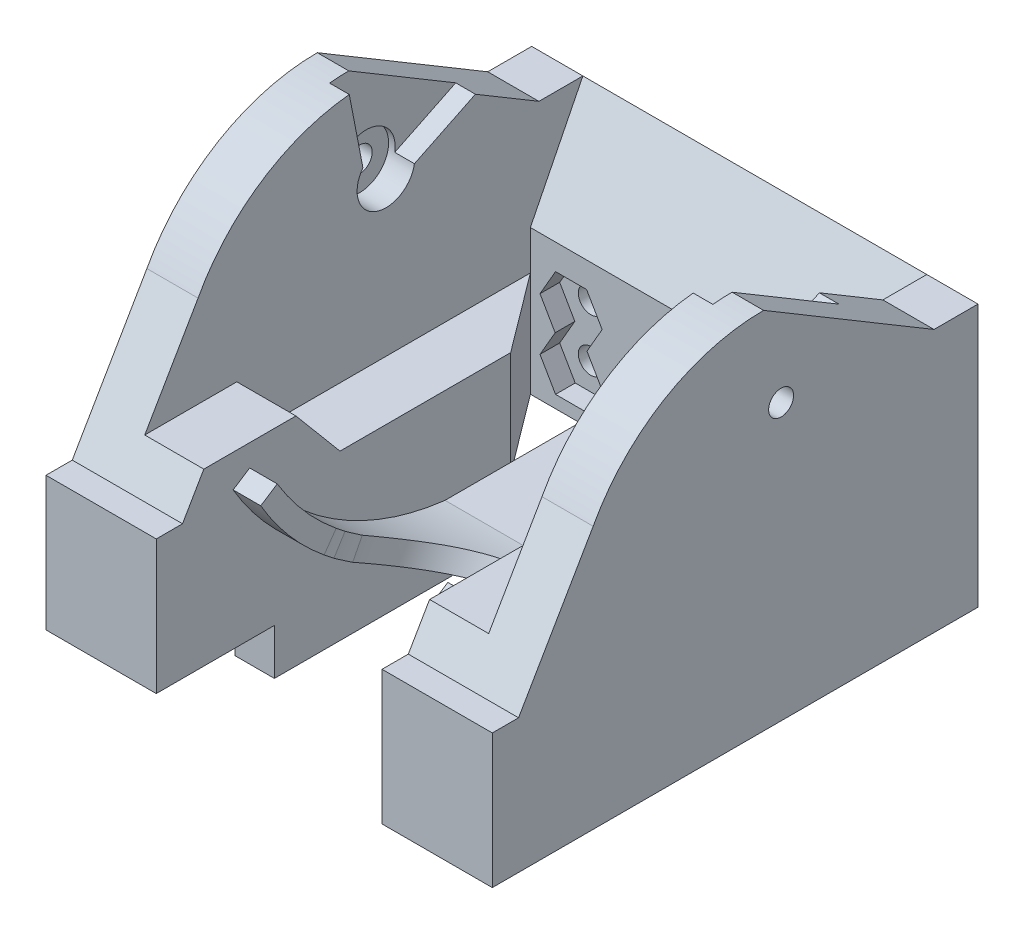
SolidWorks part; units mm, degrees
ref_plane "Alzado" through (0, 0, 0) normal (0, 0, 1) x (1, 0, 0)
ref_plane "Planta" through (0, 0, 0) normal (0, 1, 0) x (1, 0, 0)
ref_plane "Vista lateral" through (0, 0, 0) normal (1, 0, 0) x (0, 0, -1)
sketch "Croquis1" plane through (0, 0, 0) normal (0, 0, 1) x (1, 0, 0)
  line L1 (-48.8873, 14.6225) -> (-14.8873, 14.6225)
  line L2 (-48.8873, 14.6225) -> (-48.8873, -4.3775)
  line L3 (-48.8873, -4.3775) -> (-14.8873, -4.3775)
  line L4 (-14.8873, 14.6225) -> (-14.8873, -4.3775)
  dimension "D1" = 19
  dimension "D2" = 34
extrude "Saliente-Extruir1" add sketch "Croquis1" along normal blind 35
sketch "Croquis2" plane through (0, -4.3775, 0) normal (0, -1, 0) x (1, 0, 0)
  line L0 (-48.8873, 35) -> (-14.8873, 35) construction
  line L1 (-44.9873, 35) -> (-18.7873, 35)
  line L2 (-44.9873, 35) -> (-44.9873, 4)
  line L3 (-44.9873, 4) -> (-18.7873, 4)
  line L4 (-18.7873, 35) -> (-18.7873, 4)
  line L5 (-48.8873, 35) -> (-48.8873, 0) construction
  line L6 (-14.8873, 35) -> (-14.8873, 0) construction
  line L7 (-48.8873, 0) -> (-14.8873, 0) construction
  dimension "D1" = 3.9
  dimension "D2" = 3.9
  dimension "D3" = 26.2
  dimension "D4" = 4
extrude "Cortar-Extruir1" cut sketch "Croquis2" against normal blind 25
sketch "Croquis4" plane through (-18.7873, 0, 0) normal (-1, 0, 0) x (0, 0, 1)
  line L0 (4, 14.6225) -> (4, 6.6225)
  line L1 (4, 14.6225) -> (4, -4.3775) construction
  line L2 (4, 6.6225) -> (0, 14.6225)
  line L3 (0, 14.6225) -> (4, 14.6225)
extrude "Cortar-Extruir3" cut sketch "Croquis4" along normal up to vertex (26.2 mm away) up to point (-44.9873, 14.6225, 4)
sketch "Croquis9" plane through (-14.8873, 0, 0) normal (1, 0, 0) x (0, 0, -1)
  line L0 (-35, 14.6225) -> (0, 14.6225) construction
  line L1 (-29.3158, 14.6225) -> (-3.3495, 14.6225)
  line L7 (-35, -4.3775) -> (0, -4.3775) construction
  arc A0 (-29.3158, 14.6225) -> (-3.3495, 14.6225) centre (-16.3327, 7.6225) cw
  dimension "D2" = 12
extrude "Saliente-Extruir2" add sketch "Croquis9" against normal up to vertex (34 mm away) up to point (-48.8873, 14.6225, 35)
sketch "Croquis10" plane through (0, 14.6225, 0) normal (0, -1, 0) x (1, 0, 0)
  line L1 (-44.9873, 29.3158) -> (-18.7873, 29.3158)
  line L2 (-44.9873, 29.3158) -> (-44.9873, 3.3495)
  line L3 (-44.9873, 3.3495) -> (-18.7873, 3.3495)
  line L4 (-18.7873, 29.3158) -> (-18.7873, 3.3495)
extrude "Cortar-Extruir4" cut sketch "Croquis10" against normal blind 10
sketch "Croquis18" plane through (0, 0, 0) normal (0, 0, -1) x (-1, 0, 0)
  line L0 (48.8873, -4.3775) -> (14.8873, -4.3775) construction
  line L2 (48.8873, 14.6225) -> (48.8873, -4.3775) construction
  circle A0 centre (41.8873, -1.3775) radius 0.95
  circle A1 centre (21.8873, -1.3775) radius 0.95
  circle A2 centre (21.8873, 2.6225) radius 0.95
  circle A3 centre (41.8873, 2.6225) radius 0.95
  dimension "D1" = 3
  dimension "D2" = 7
  dimension "D5" = 4
  dimension "D3" = 2
  dimension "D4" = 2
extrude "Cortar-Extruir11" cut sketch "Croquis18" against normal up to vertex (4 mm away) up to point (-18.7873, -4.3775, 4)
sketch "Croquis19" plane through (0, 0, 4) normal (0, 0, 1) x (1, 0, 0)
  line L0 (-44.2544, -1.3775) -> (-43.0708, -3.4275)
  line L1 (-24.2544, -1.3775) -> (-23.0708, -3.4275)
  line L2 (-23.0708, -3.4275) -> (-20.7037, -3.4275)
  line L3 (-20.7037, -3.4275) -> (-19.5201, -1.3775)
  line L4 (-19.5201, -1.3775) -> (-20.6748, 0.6225)
  line L6 (-23.0997, 0.6225) -> (-24.2544, -1.3775)
  line L7 (-43.0708, -3.4275) -> (-40.7037, -3.4275)
  line L8 (-40.7037, -3.4275) -> (-39.5201, -1.3775)
  line L9 (-39.5201, -1.3775) -> (-40.6748, 0.6225)
  line L11 (-43.0997, 0.6225) -> (-44.2544, -1.3775)
  line L12 (-44.2544, 2.6225) -> (-43.0997, 0.6225)
  line L14 (-40.6748, 0.6225) -> (-39.5201, 2.6225)
  line L15 (-39.5201, 2.6225) -> (-40.7037, 4.6725)
  line L16 (-40.7037, 4.6725) -> (-43.0708, 4.6725)
  line L17 (-43.0708, 4.6725) -> (-44.2544, 2.6225)
  line L18 (-24.2544, 2.6225) -> (-23.0997, 0.6225)
  line L20 (-20.6748, 0.6225) -> (-19.5201, 2.6225)
  line L21 (-19.5201, 2.6225) -> (-20.7037, 4.6725)
  line L22 (-20.7037, 4.6725) -> (-23.0708, 4.6725)
  line L23 (-23.0708, 4.6725) -> (-24.2544, 2.6225)
  line L52 (-20.7037, 0.6725) -> (-23.0708, 0.6725) [skipped]
  line L53 (-23.0708, 0.5725) -> (-20.7037, 0.5725) [skipped]
  line L54 (-43.0708, 0.5725) -> (-40.7037, 0.5725) [skipped]
  circle A0 centre (-21.8873, -1.3775) radius 2.05 construction
  circle A1 centre (-41.8873, -1.3775) radius 2.05 construction
  circle A2 centre (-41.8873, 2.6225) radius 2.05 construction
  circle A3 centre (-21.8873, 2.6225) radius 2.05 construction
  dimension "D2" = 2
  dimension "D3" = 2
extrude "Cortar-Extruir12" cut sketch "Croquis19" against normal blind 1.5
sketch "Croquis21" plane through (-14.8873, 0, 0) normal (1, 0, 0) x (0, 0, -1)
  line L0 (0, -4.3775) -> (0, 14.6225) construction
  line L2 (-35, -4.3775) -> (0, -4.3775) construction
  circle A0 centre (-15, 15.6225) radius 0.95
  dimension "D1" = 15
  dimension "D2" = 20
extrude "Cortar-Extruir14" cut sketch "Croquis21" against normal up to vertex (34 mm away) up to point (-48.8873, 14.6225, 3.3495)
sketch "Croquis23" plane through (0, -4.3775, 0) normal (0, -1, 0) x (1, 0, 0)
  line L0 (-44.9873, 35) -> (-40.4873, 35)
  line L1 (-40.4873, 35) -> (-40.4873, 10)
  line L2 (-40.4873, 10) -> (-44.9873, 4)
  line L3 (-44.9873, 35) -> (-44.9873, 4) construction
  line L4 (-44.9873, 4) -> (-44.9873, 35)
  line L5 (-18.7873, 35) -> (-23.2873, 35)
  line L6 (-23.2873, 35) -> (-23.2873, 10)
  line L7 (-23.2873, 10) -> (-18.7873, 4)
  line L8 (-18.7873, 4) -> (-18.7873, 35)
  dimension "D1" = 25
  dimension "D2" = 25
extrude "Saliente-Extruir3" add sketch "Croquis23" against normal blind 8
sketch "Croquis25" plane through (0, -4.3775, 0) normal (0, -1, 0) x (1, 0, 0)
  line L0 (-40.4873, 35) -> (-43.4873, 35)
  line L1 (-20.2873, 35) -> (-23.2873, 35)
  line L2 (-43.4873, 35) -> (-43.4873, 10)
  line L3 (-43.4873, 10) -> (-40.4873, 10)
  line L4 (-40.4873, 35) -> (-40.4873, 10)
  line L10 (-20.2873, 35) -> (-20.2873, 10)
  line L11 (-20.2873, 10) -> (-23.2873, 10)
  line L12 (-23.2873, 35) -> (-23.2873, 10)
  dimension "D1" = 3
  dimension "D2" = 3
extrude "Saliente-Extruir4" add sketch "Croquis25" along normal blind 3
sketch "Croquis43" plane through (0, 3.6225, 0) normal (0, 1, 0) x (1, 0, 0)
  line L0 (-23.2873, -35) -> (-23.2873, -10) construction
  line L1 (-18.7873, -35) -> (-23.2873, -35)
  line L2 (-18.7873, -35) -> (-18.7873, -23)
  line L3 (-18.7873, -23) -> (-23.2873, -23)
  line L4 (-23.2873, -35) -> (-23.2873, -23)
  line L5 (-44.9873, -35) -> (-44.9873, -4) construction
  line L6 (-40.4873, -35) -> (-44.9873, -35)
  line L7 (-40.4873, -35) -> (-40.4873, -23)
  line L8 (-40.4873, -23) -> (-44.9873, -23)
  line L9 (-44.9873, -35) -> (-44.9873, -23)
  dimension "D1" = 12
  dimension "D2" = 12
extrude "Saliente-Extruir8" add sketch "Croquis43" along normal blind 4
sketch "Croquis27" plane through (-14.8873, 0, 0) normal (1, 0, 0) x (0, 0, -1)
  line L0 (-13.5494, -0.9426) -> (-12.6355, -5.8873)
  line L1 (-33.492, 4.3837) -> (-29.3712, 7.2574)
  arc A2 (-29.3712, 7.2574) -> (-13.5494, -0.9426) centre (-15, 15.6225) ccw
  arc A3 (-33.492, 4.3837) -> (-12.6355, -5.8873) centre (-15, 15.6225) ccw
  dimension "D2" = 21.6395
sketch "Croquis29" plane through (-18.7873, 0, 0) normal (-1, 0, 0) x (0, 0, 1)
  line L0 (17.7974, 22.2996) -> (16.5, 15.6225)
  line L1 (6.2969, 18.4321) -> (13.7431, 14.804)
  arc A0 (6.2969, 18.4321) -> (17.7974, 22.2996) centre (16.3327, 7.6225) cw
  arc A1 (29.3158, 14.6225) -> (3.3495, 14.6225) centre (16.3327, 7.6225) ccw construction
  arc A2 (16.5, 15.6225) -> (13.7431, 14.804) centre (15, 15.6225) cw
extrude "Cortar-Extruir20" cut sketch "Croquis29" against normal blind 1.5
extrude "Cortar-Extruir21" cut sketch "Croquis29<2>" along normal blind 27.7
sketch "Croquis29<2>" plane through (-18.7873, 0, 0) normal (-1, 0, 0) x (0, 0, 1) same geometry as "Croquis29"
sketch "Croquis30" plane through (-48.8873, 0, 0) normal (-1, 0, 0) x (0, 0, 1)
  line L0 (29.3158, 14.6225) -> (35, 4.8278)
  line L1 (35, 14.6225) -> (35, -4.3775) construction
  line L2 (35, 4.8278) -> (35, 14.6225)
  line L3 (35, 14.6225) -> (29.3158, 14.6225)
extrude "Cortar-Extruir22" cut sketch "Croquis30" against normal up to vertex (34 mm away) up to point (-14.8873, 14.6225, 35)
sketch "Croquis35" plane through (0, -4.3775, 0) normal (0, -1, 0) x (1, 0, 0)
  line L0 (-20.2873, 23.2623) -> (-14.8873, 23.2623)
  line L2 (-20.2873, 23.2623) -> (-14.8873, 23.2623) construction
  line L4 (-14.8873, 23.2623) -> (-14.8873, 27.7963)
  line L5 (-14.8873, 35) -> (-14.8873, 0) construction
  line L6 (-14.8873, 27.7963) -> (-20.2873, 23.2623)
sketch "Croquis36" plane through (-18.7873, 0, 0) normal (-1, 0, 0) x (0, 0, 1)
  circle A0 centre (15, 15.6225) radius 2.2
extrude "Cortar-Extruir24" cut sketch "Croquis36" against normal blind 2
extrude "Cortar-Extruir25" cut sketch "Croquis36<2>" along normal blind 28.2
sketch "Croquis36<2>" plane through (-18.7873, 0, 0) normal (-1, 0, 0) x (0, 0, 1) same geometry as "Croquis36"
sketch "Croquis38" plane through (-48.8873, 0, 0) normal (-1, 0, 0) x (0, 0, 1)
  line L0 (3.3495, 14.6225) -> (16.3327, 22.3725)
  line L1 (16.3327, 22.3725) -> (3.3495, 22.3725)
  line L2 (3.3495, 22.3725) -> (3.3495, 14.6225)
  arc A0 (29.3158, 14.6225) -> (3.3495, 14.6225) centre (16.3327, 7.6225) ccw construction
extrude "Cortar-Extruir26" cut sketch "Croquis38" against normal up to vertex (34 mm away) up to point (-14.8873, 14.6225, 3.3495)
sketch "Croquis40" plane through (-48.8873, 0, 0) normal (-1, 0, 0) x (0, 0, 1)
  line L0 (24.4625, 4.9679) -> (27.805, 0.9845)
  line L1 (27.805, 0.9845) -> (27.1921, 0.4702)
  line L2 (27.1921, 0.4702) -> (23.8496, 4.4537)
  line L3 (23.5, 4.1807) -> (26.4826, -0.0789)
  line L4 (26.4826, -0.0789) -> (25.8272, -0.5377)
  line L5 (25.8272, -0.5377) -> (22.8446, 3.7219)
  line L6 (22.4696, 3.4848) -> (25.0696, -1.0186)
  line L7 (24.4625, 4.9679) -> (23.8496, 4.4537)
  line L8 (25.0696, -1.0186) -> (24.3768, -1.4186)
  line L9 (24.3768, -1.4186) -> (21.7768, 3.0848)
  line L10 (22.8446, 3.7219) -> (23.5, 4.1807)
  line L11 (21.3819, 2.8831) -> (23.5795, -1.8297)
  line L12 (23.5795, -1.8297) -> (22.8544, -2.1678)
  line L13 (22.4696, 3.4848) -> (21.7768, 3.0848)
  line L14 (22.8544, -2.1678) -> (20.6568, 2.545)
  line L16 (21.3819, 2.8831) -> (20.6568, 2.545)
  circle A1 centre (15, 15.6225) radius 0.95 construction
  dimension "D2" = 14.2443
  dimension "D3" = 14.248
  dimension "D4" = 14.2464
  dimension "D5" = 0.8
  dimension "D6" = 14.2429
  dimension "D8" = 0.8
  dimension "D9" = 0.8
  dimension "D11" = 0.8
sketch "Croquis41" plane through (-20.2873, 0, 0) normal (1, 0, 0) x (0, 0, -1)
  line L0 (-10, -4.3775) -> (-10, -7.3775)
  line L1 (-10, -7.3775) -> (-10, -4.3775) construction
  line L2 (-10, -7.3775) -> (-13, -7.3775)
  line L3 (-10, -7.3775) -> (-35, -7.3775) construction
  line L4 (-13, -7.3775) -> (-10, -4.3775)
extrude "Cortar-Extruir28" cut sketch "Croquis41" against normal up to vertex (23.2 mm away) up to point (-43.4873, -7.3775, 10)
sketch "Croquis44" plane through (-18.7873, 0, 0) normal (-1, 0, 0) x (0, 0, 1)
  line L0 (23, 7.6225) -> (26.3626, 7.6225)
  line L1 (33.3781, 7.6225) -> (23, 7.6225) construction
  line L2 (26.3626, 7.6225) -> (23, 3.6225)
  line L3 (23, 3.6225) -> (23, 7.6225)
extrude "Cortar-Extruir29" cut sketch "Croquis44" along normal up to vertex (26.2 mm away) up to point (-44.9873, 7.6225, 23)
sketch "Croquis24" plane through (-14.8873, 0, 0) normal (1, 0, 0) x (0, 0, -1)
  line L0 (-15, -3.6275) -> (-15, -5.1273)
  line L1 (-31.1427, 5.1356) -> (-32.3723, 4.2754)
  arc A2 (-31.1427, 5.1356) -> (-15, -3.6275) centre (-15, 15.6225) ccw
  arc A3 (-32.3723, 4.2754) -> (-15, -5.1273) centre (-15, 15.6225) ccw
  dimension "D1" = 19.25
  dimension "D2" = 20.7498
sketch "Croquis45" plane through (-23.2873, 0, 0) normal (-1, 0, 0) x (0, 0, 1)
  line L0 (15, -3.6275) -> (15, -5.1275)
  line L2 (15, -3.6275) -> (15, -5.1273) construction
  line L3 (15, 15.6225) -> (31.1427, 5.1356) construction
  line L4 (15, -3.6275) -> (15, 15.6225) construction
  line L5 (31.1427, 5.1356) -> (29.8848, 5.9527)
  arc A0 (15, -3.6275) -> (31.1427, 5.1356) centre (15, 15.6225) ccw construction
  arc A1 (31.1427, 5.1356) -> (15, -5.1275) centre (13.1536, 15.6036) cw
  arc A4 (15, -3.6275) -> (29.8848, 5.9527) centre (12.6596, 16.3623) ccw
extrude "Saliente-Extruir9" add sketch "Croquis45" along normal up to vertex (17.2 mm away) separate body up to point (-40.4873, -7.3775, 13)
ref_plane "Plano1" through (-31.8873, 4.2754, 32.3723) normal (1, 0, 0) x (0, 0, -1)
sketch "Croquis47" plane through (-31.8873, 4.2754, 32.3723) normal (1, 0, 0) x (0, 0, -1)
  line L0 (17.3723, 11.3471) -> (17.3723, -21.3789) construction
  line L1 (17.3723, 11.3471) -> (0.4676, -24.9052) construction
  line L2 (17.3723, 11.3471) -> (-2.6277, -23.2939) construction
  line L3 (17.3723, 11.3471) -> (-5.5707, -21.419) construction
  line L4 (17.3723, 11.3471) -> (-5.5707, -21.419)
  line L5 (17.3723, 11.3471) -> (-2.6277, -23.2939)
  line L6 (17.3723, 11.3471) -> (0.4676, -24.9052)
  dimension "D1" = 25
  dimension "D2" = 30
  dimension "D3" = 35
ref_plane "Plano2" through (-31.8873, -17.1435, 37.9431) normal (0, -0.8192, 0.5736) x (-1, 0, 0)
sketch "Croquis48" plane through (-31.8873, -17.1435, 37.9431) normal (0, -0.8192, 0.5736) x (-1, 0, 0)
  line L3 (6.5, 0) -> (6.5, -15)
  line L4 (6.5, -15) -> (-6.5, -15)
  line L5 (-6.5, -15) -> (-6.5, 0)
  arc A2 (6.5, 0) -> (-6.5, 0) centre (0, 0) ccw
ref_plane "Plano3" through (-31.8873, -19.0185, 35) normal (0, -0.866, 0.5) x (-1, 0, 0)
ref_plane "Plano4" through (-31.8873, -20.6298, 31.9047) normal (0, -0.9063, 0.4226) x (-1, 0, 0)
sketch "Croquis49" plane through (-31.8873, -19.0185, 35) normal (0, -0.866, 0.5) x (-1, 0, 0)
  circle A0 centre (0, 0) radius 6.5
sketch "Croquis50" plane through (-31.8873, -20.6298, 31.9047) normal (0, -0.9063, 0.4226) x (-1, 0, 0)
  circle A0 centre (0, 0) radius 6.5
sweep "Cortar-Barrer2" cut profiles "Croquis48" path "Croquis47"
sketch "Croquis51" plane through (-31.8873, 4.2754, 32.3723) normal (1, 0, 0) x (0, 0, -1)
  line L0 (17.3723, 11.3471) -> (-2.6277, -23.2939)
sweep "Cortar-Barrer3" cut profiles "Croquis49" path "Croquis51"
sketch "Croquis52" plane through (-31.8873, 4.2754, 32.3723) normal (1, 0, 0) x (0, 0, -1)
  line L0 (17.3723, 11.3471) -> (0.4676, -24.9052)
sweep "Cortar-Barrer4" cut profiles "Croquis50" path "Croquis52"
sketch "Croquis56" plane through (0, 0, 35) normal (0, 0, 1) x (1, 0, 0)
  line L0 (-23.2873, -7.3775) -> (-20.2873, -7.3775)
  line L1 (-20.2873, -7.3775) -> (-20.2873, -4.3775)
  line L2 (-20.2873, -4.3775) -> (-14.8873, -4.3775)
  line L3 (-14.8873, -4.3775) -> (-14.8873, 4.8278)
  line L4 (-14.8873, 4.8278) -> (-23.2873, 4.8278)
  line L5 (-23.2873, 4.8278) -> (-23.2873, -7.3775)
  line L6 (-40.4873, -7.3775) -> (-40.4873, 4.8278)
  line L7 (-40.4873, 4.8278) -> (-48.8873, 4.8278)
  line L8 (-48.8873, 4.8278) -> (-48.8873, -4.3775)
  line L9 (-48.8873, -4.3775) -> (-43.4873, -4.3775)
  line L10 (-43.4873, -4.3775) -> (-43.4873, -7.3775)
  line L11 (-43.4873, -7.3775) -> (-40.4873, -7.3775)
extrude "Saliente-Extruir15" add sketch "Croquis56" along normal blind 2
sketch "Croquis58" plane through (0, 0, 37) normal (0, 0, 1) x (1, 0, 0)
  line L0 (-40.4873, -7.3775) -> (-40.4873, 4.8278) construction
  line L2 (-40.4873, -1.2748) -> (-40.4873, 6.807)
  line L3 (-40.4873, 6.807) -> (-23.2873, 6.807)
  line L4 (-23.2873, -1.2748) -> (-23.2873, 6.807)
  line L5 (-23.2873, -1.2748) -> (-23.2873, -3.2748)
  line L6 (-23.2873, 4.8278) -> (-23.2873, -7.3775) construction
  line L7 (-23.2873, -3.2748) -> (-40.4873, -3.2748)
  line L8 (-40.4873, -3.2748) -> (-40.4873, -1.2748)
sketch "Croquis60" plane through (0, -4.3775, 0) normal (0, -1, 0) x (1, 0, 0)
  line L1 (-48.8873, 35) -> (-48.8873, 0)
  line L2 (-43.4873, 35) -> (-43.4873, 10)
  line L3 (-43.4873, 10) -> (-48.8873, 0)
  line L4 (-14.8873, 0) -> (-14.8873, 37)
  line L5 (-14.8873, 37) -> (-20.2873, 37)
  line L6 (-20.2873, 37) -> (-20.2873, 10)
  line L7 (-20.2873, 10) -> (-14.8873, 0)
  line L9 (-48.8873, 35) -> (-48.8873, 37)
  line L10 (-48.8873, 37) -> (-43.4873, 37)
  line L11 (-43.4873, 37) -> (-43.4873, 35)
extrude "Saliente-Extruir30" add sketch "Croquis60" along normal blind 1
sketch "Croquis61" plane through (0, 0, 15) normal (0, 0, -1) x (-1, 0, 0)
  line L0 (23.2873, -3.6275) -> (23.2873, -5.1275) construction
  line L1 (40.4873, -5.1275) -> (23.2873, -5.1275)
  line L2 (40.4873, -5.1275) -> (40.4873, -3.6275)
  line L3 (40.4873, -3.6275) -> (23.2873, -3.6275)
  line L4 (23.2873, -5.1275) -> (23.2873, -3.6275)
  line L5 (40.4873, -3.6275) -> (23.2873, -3.6275) construction
extrude "Saliente-Extruir31" add sketch "Croquis61" along normal up to vertex (11 mm away) up to point (-18.7873, -4.3775, 4)
sketch "Croquis62" plane through (-23.2873, 0, 0) normal (1, 0, 0) x (0, 0, -1)
  line L0 (-4, -4.3775) -> (-4, -5.1275)
  line L1 (-4, -5.1275) -> (0, -4.3775)
  line L2 (0, -4.3775) -> (-4, -4.3775)
extrude "Saliente-Extruir32" add sketch "Croquis62" against normal up to vertex (17.2 mm away) up to point (-40.4873, -4.3775, 4)
sketch "Croquis63" plane through (0, -7.3775, 0) normal (0, -1, 0) x (1, 0, 0)
  line L0 (-43.4873, 37) -> (-43.4873, 13) construction
  line L1 (-40.4873, 13) -> (-43.4873, 13)
  line L2 (-40.4873, 13) -> (-40.4873, 28)
  line L3 (-40.4873, 28) -> (-43.4873, 28)
  line L4 (-43.4873, 13) -> (-43.4873, 28)
  line L5 (-23.2873, 37) -> (-23.2873, 13) construction
  line L6 (-20.2873, 13) -> (-23.2873, 13)
  line L7 (-20.2873, 13) -> (-20.2873, 28)
  line L8 (-20.2873, 28) -> (-23.2873, 28)
  line L9 (-23.2873, 13) -> (-23.2873, 28)
  dimension "D1" = 15
extrude "Saliente-Extruir33" add sketch "Croquis63" along normal blind 1.5
sketch "Croquis64" plane through (0, -7.3775, 0) normal (0, -1, 0) x (1, 0, 0)
  line L1 (-43.4873, 37) -> (-20.2873, 37)
  line L2 (-43.4873, 37) -> (-43.4873, 28)
  line L3 (-43.4873, 28) -> (-20.2873, 28)
  line L4 (-20.2873, 37) -> (-20.2873, 28)
extrude "Cortar-Extruir30" cut sketch "Croquis64" against normal up to vertex (2 mm away) up to point (-20.2873, -5.3775, 37)
sketch "Croquis65" plane through (-43.4873, 0, 0) normal (-1, 0, 0) x (0, 0, 1)
  line L0 (13, -7.3775) -> (14.5, -8.8775)
  line L1 (28, -8.8775) -> (13, -8.8775) construction
  line L2 (14.5, -8.8775) -> (13, -8.8775)
  line L3 (13, -8.8775) -> (13, -7.3775)
extrude "Cortar-Extruir31" cut sketch "Croquis65" against normal up to vertex (23.2 mm away) up to point (-20.2873, -8.8775, 13)
